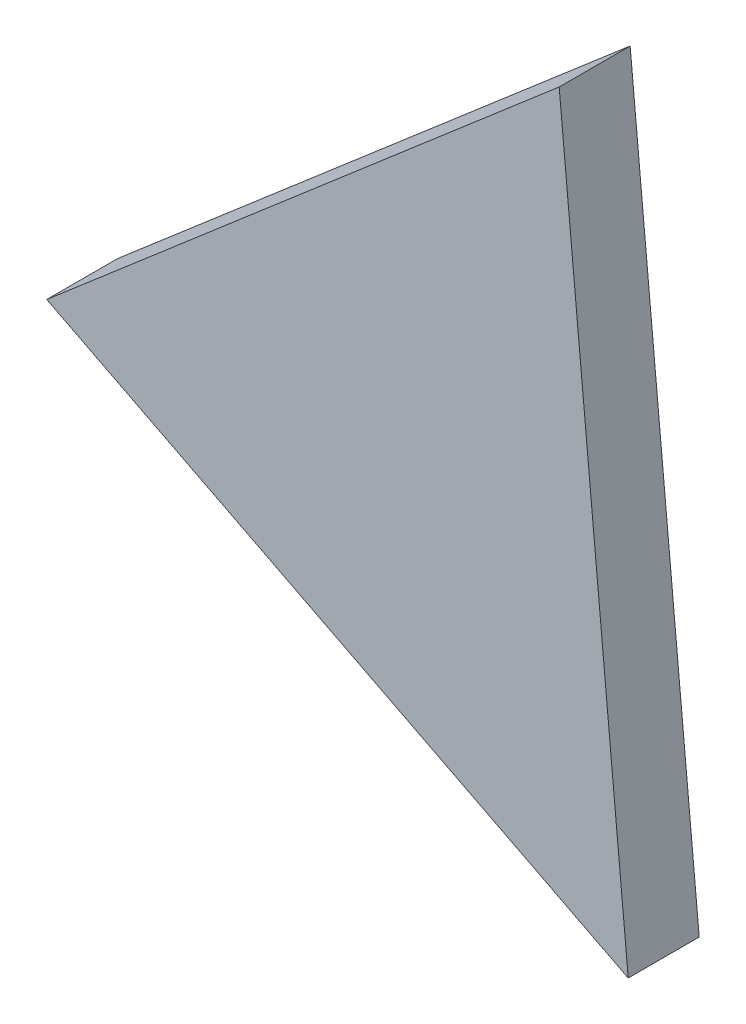
SolidWorks part; units mm, degrees
ref_plane "Front Plane" through (0, 0, 0) normal (0, 0, 1) x (1, 0, 0)
ref_plane "Top Plane" through (0, 0, 0) normal (0, 1, 0) x (1, 0, 0)
ref_plane "Right Plane" through (0, 0, 0) normal (1, 0, 0) x (0, 0, -1)
sketch "Sketch1" plane through (0, 0, 0) normal (0, 0, 1) x (1, 0, 0)
  line L0 (78.4194, -149.7709) -> (49.2291, 161.7333)
  line L1 (49.2291, 161.7333) -> (-167.3043, -24.2993)
  line L2 (-167.3043, -24.2993) -> (78.4194, -149.7709)
extrude "Boss-Extrude1" add sketch "Sketch1" along normal blind 30
equation "\"D1@Boss-Extrude1\"=\"wall_thick@4Vcorrection.Assembly\""
